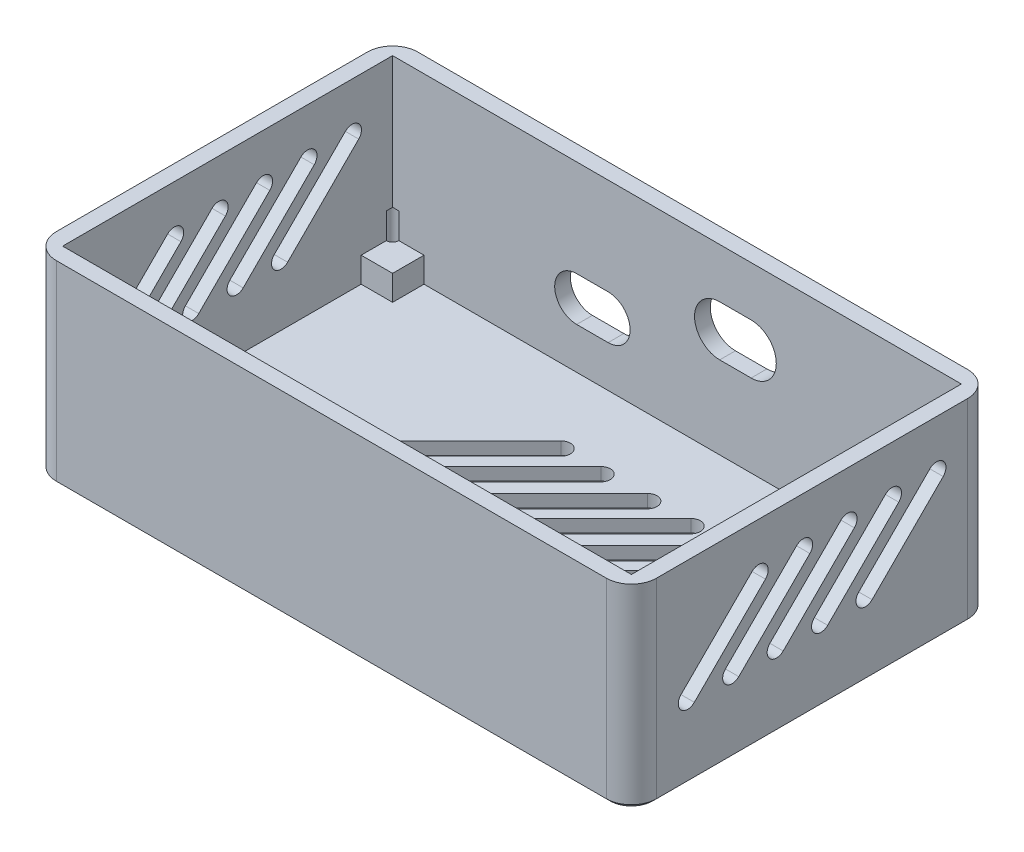
SolidWorks part; units mm, degrees
ref_plane "Front Plane" through (0, 0, 0) normal (0, 0, 1) x (1, 0, 0)
ref_plane "Top Plane" through (0, 0, 0) normal (0, 1, 0) x (1, 0, 0)
ref_plane "Right Plane" through (0, 0, 0) normal (1, 0, 0) x (0, 0, -1)
sketch "Croquis_contorno" plane through (0, 0, 0) normal (0, 1, 0) x (1, 0, 0)
  line L0 (-43.75, -28.75) -> (43.75, -28.75)
  line L1 (47.75, -24.75) -> (47.75, 24.75)
  line L2 (43.75, 28.75) -> (-43.75, 28.75)
  line L3 (-47.75, 24.75) -> (-47.75, -24.75)
  arc A0 (43.75, -28.75) -> (47.75, -24.75) centre (43.75, -24.75) ccw
  arc A1 (47.75, 24.75) -> (43.75, 28.75) centre (43.75, 24.75) ccw
  arc A2 (-43.75, 28.75) -> (-47.75, 24.75) centre (-43.75, 24.75) ccw
  arc A3 (-47.75, -24.75) -> (-43.75, -28.75) centre (-43.75, -24.75) ccw
  dimension "D3" = 4
  dimension "D1" = 95.5
  dimension "D2" = 57.5
extrude "Cuerpo" add sketch "Croquis_contorno" along normal blind 31
ref_plane "Plano_Top Plane_+31" through (0, 31, 0) normal (0, 1, 0) x (1, 0, 0)
sketch "Croquis_hueco_PCB" plane through (0, 31, 0) normal (0, 1, 0) x (1, 0, 0)
  line L1 (-45.25, -26.25) -> (45.25, -26.25)
  line L2 (-45.25, -26.25) -> (-45.25, 26.25)
  line L3 (-45.25, 26.25) -> (45.25, 26.25)
  line L4 (45.25, -26.25) -> (45.25, 26.25)
  line L5 (-45.25, -26.25) -> (45.25, 26.25) construction
  line L6 (-45.25, 26.25) -> (45.25, -26.25) construction
  dimension "D1" = 90.5
  dimension "D2" = 52.5
extrude "Hueco_PCB" cut sketch "Croquis_hueco_PCB" against normal blind 29
ref_plane "Plano_Top Plane_+2" through (0, 2, 0) normal (0, 1, 0) x (1, 0, 0)
sketch "Croquis_apoyos" plane through (0, 2, 0) normal (0, 1, 0) x (1, 0, 0)
  line L0 (45.25, 26.25) -> (-45.25, 26.25) construction
  line L1 (-45.25, -26.25) -> (-40.25, -26.25)
  line L2 (-45.25, -26.25) -> (-45.25, -21.25)
  line L3 (-45.25, -21.25) -> (-40.25, -21.25)
  line L4 (-40.25, -26.25) -> (-40.25, -21.25)
  line L5 (-45.25, -26.25) -> (-40.25, -21.25) construction
  line L6 (-45.25, -21.25) -> (-40.25, -26.25) construction
  line L7 (-45.25, 21.25) -> (-40.25, 21.25)
  line L8 (-45.25, 21.25) -> (-45.25, 26.25)
  line L9 (-45.25, 26.25) -> (-40.25, 26.25)
  line L10 (-40.25, 21.25) -> (-40.25, 26.25)
  line L11 (-45.25, 21.25) -> (-40.25, 26.25) construction
  line L12 (-45.25, 26.25) -> (-40.25, 21.25) construction
  line L13 (45.25, -26.25) -> (45.25, 26.25) construction
  line L14 (40.25, -26.25) -> (45.25, -26.25)
  line L15 (40.25, -26.25) -> (40.25, -21.25)
  line L16 (40.25, -21.25) -> (45.25, -21.25)
  line L17 (45.25, -26.25) -> (45.25, -21.25)
  line L18 (40.25, -26.25) -> (45.25, -21.25) construction
  line L19 (40.25, -21.25) -> (45.25, -26.25) construction
  line L21 (40.25, 21.25) -> (45.25, 21.25)
  line L22 (40.25, 21.25) -> (40.25, 26.25)
  line L23 (40.25, 26.25) -> (45.25, 26.25)
  line L24 (45.25, 21.25) -> (45.25, 26.25)
  line L25 (40.25, 21.25) -> (45.25, 26.25) construction
  line L26 (40.25, 26.25) -> (45.25, 21.25) construction
  point P0 (-42.75, 23.75)
  point P11 (42.75, -23.75)
  point P18 (42.75, 23.75)
  dimension "D1" = 5
  dimension "D2" = 5
extrude "Apoyos_PCB" add sketch "Croquis_apoyos" along normal blind 4
sketch "Croquis_alivios" plane through (0, 2, 0) normal (0, 1, 0) x (1, 0, 0)
  circle A0 centre (-45.25, -26.25) radius 1
  circle A1 centre (-45.25, 26.25) radius 1
  circle A2 centre (45.25, -26.25) radius 1
  circle A3 centre (45.25, 26.25) radius 1
  dimension "D1" = 2
extrude "Alivios_esquinas" cut sketch "Croquis_alivios" along normal blind 8.1
sketch "Croquis_salidas" plane through (0, 0, 0) normal (0, 0, 1) x (1, 0, 0)
  line L0 (6.8, 19.1) -> (11.8, 19.1) construction
  line L1 (6.8, 23.1) -> (11.8, 23.1)
  line L2 (6.8, 15.1) -> (11.8, 15.1)
  line L3 (-15.96, 12.1) -> (-10.96, 12.1) construction
  line L4 (-15.96, 15.6) -> (-10.96, 15.6)
  line L5 (-15.96, 8.6) -> (-10.96, 8.6)
  arc A0 (6.8, 23.1) -> (6.8, 15.1) centre (6.8, 19.1) ccw
  arc A1 (11.8, 15.1) -> (11.8, 23.1) centre (11.8, 19.1) ccw
  arc A2 (-15.96, 15.6) -> (-15.96, 8.6) centre (-15.96, 12.1) ccw
  arc A3 (-10.96, 8.6) -> (-10.96, 15.6) centre (-10.96, 12.1) ccw
  point P2 (9.3, 19.1)
  point P7 (-13.46, 12.1)
  point P14 (0, 0)
extrude "Salidas_USB_y_panel" cut sketch "Croquis_salidas" against normal through all
sketch "Croquis_ventilas" plane through (0, 0, 0) normal (1, 0, 0) x (0, 0, -1)
  line L0 (-19.799, 11.9431) -> (-8.4853, 23.2569) construction
  line L1 (-20.8597, 13.0038) -> (-9.5459, 24.3175)
  line L2 (-18.7383, 10.8825) -> (-7.4246, 22.1962)
  line L3 (-12.7279, 11.9431) -> (-1.4142, 23.2569) construction
  line L4 (-13.7886, 13.0038) -> (-2.4749, 24.3175)
  line L5 (-11.6673, 10.8825) -> (-0.3536, 22.1962)
  line L6 (-5.6569, 11.9431) -> (5.6569, 23.2569) construction
  line L7 (-6.7175, 13.0038) -> (4.5962, 24.3175)
  line L8 (-4.5962, 10.8825) -> (6.7175, 22.1962)
  line L9 (1.4142, 11.9431) -> (12.7279, 23.2569) construction
  line L10 (0.3536, 13.0038) -> (11.6673, 24.3175)
  line L11 (2.4749, 10.8825) -> (13.7886, 22.1962)
  line L12 (8.4853, 11.9431) -> (19.799, 23.2569) construction
  line L13 (7.4246, 13.0038) -> (18.7383, 24.3175)
  line L14 (9.5459, 10.8825) -> (20.8597, 22.1962)
  arc A0 (-20.8597, 13.0038) -> (-18.7383, 10.8825) centre (-19.799, 11.9431) ccw
  arc A1 (-7.4246, 22.1962) -> (-9.5459, 24.3175) centre (-8.4853, 23.2569) ccw
  arc A2 (-13.7886, 13.0038) -> (-11.6673, 10.8825) centre (-12.7279, 11.9431) ccw
  arc A3 (-0.3536, 22.1962) -> (-2.4749, 24.3175) centre (-1.4142, 23.2569) ccw
  arc A4 (-6.7175, 13.0038) -> (-4.5962, 10.8825) centre (-5.6569, 11.9431) ccw
  arc A5 (6.7175, 22.1962) -> (4.5962, 24.3175) centre (5.6569, 23.2569) ccw
  arc A6 (0.3536, 13.0038) -> (2.4749, 10.8825) centre (1.4142, 11.9431) ccw
  arc A7 (13.7886, 22.1962) -> (11.6673, 24.3175) centre (12.7279, 23.2569) ccw
  arc A8 (7.4246, 13.0038) -> (9.5459, 10.8825) centre (8.4853, 11.9431) ccw
  arc A9 (20.8597, 22.1962) -> (18.7383, 24.3175) centre (19.799, 23.2569) ccw
  point P2 (-14.1421, 17.6)
  point P7 (-7.0711, 17.6)
  point P14 (0, 17.6)
  point P21 (7.0711, 17.6)
  point P28 (14.1421, 17.6)
  point P35 (0, 0)
extrude "Ventilas_laterales" cut sketch "Croquis_ventilas" along normal through all and the other way through all
sketch "Croquis_rejilla_piso" plane through (0, 0, 0) normal (0, 1, 0) x (1, 0, 0)
  line L0 (-35.7089, -14.4957) -> (-6.7175, 14.4957) construction
  line L1 (-36.7696, -13.435) -> (-7.7782, 15.5563)
  line L2 (-34.6482, -15.5563) -> (-5.6569, 13.435)
  line L3 (-28.6378, -14.4957) -> (0, 14.1421) construction
  line L4 (-29.6985, -13.435) -> (-1.0607, 15.2028)
  line L5 (-27.5772, -15.5563) -> (1.0607, 13.0815)
  line L6 (-21.2132, -14.4957) -> (7.4246, 14.1421) construction
  line L7 (-22.2739, -13.435) -> (6.364, 15.2028)
  line L8 (-20.1525, -15.5563) -> (8.4853, 13.0815)
  line L9 (-14.3189, -14.4957) -> (14.3189, 14.1421) construction
  line L10 (-15.3796, -13.435) -> (13.2583, 15.2028)
  line L11 (-13.2583, -15.5563) -> (15.3796, 13.0815)
  line L12 (-6.8943, -14.4957) -> (21.7435, 14.1421) construction
  line L13 (-7.955, -13.435) -> (20.6829, 15.2028)
  line L14 (-5.8336, -15.5563) -> (22.8042, 13.0815)
  line L15 (0, -14.4957) -> (28.6378, 14.1421) construction
  line L16 (-1.0607, -13.435) -> (27.5772, 15.2028)
  line L17 (1.0607, -15.5563) -> (29.6985, 13.0815)
  line L18 (6.364, -14.4957) -> (35.5321, 14.6725) construction
  line L19 (5.3033, -13.435) -> (34.4715, 15.7331)
  line L20 (7.4246, -15.5563) -> (36.5928, 13.6118)
  arc A0 (-36.7696, -13.435) -> (-34.6482, -15.5563) centre (-35.7089, -14.4957) ccw
  arc A1 (-5.6569, 13.435) -> (-7.7782, 15.5563) centre (-6.7175, 14.4957) ccw
  arc A2 (-29.6985, -13.435) -> (-27.5772, -15.5563) centre (-28.6378, -14.4957) ccw
  arc A3 (1.0607, 13.0815) -> (-1.0607, 15.2028) centre (0, 14.1421) ccw
  arc A4 (-22.2739, -13.435) -> (-20.1525, -15.5563) centre (-21.2132, -14.4957) ccw
  arc A5 (8.4853, 13.0815) -> (6.364, 15.2028) centre (7.4246, 14.1421) ccw
  arc A6 (-15.3796, -13.435) -> (-13.2583, -15.5563) centre (-14.3189, -14.4957) ccw
  arc A7 (15.3796, 13.0815) -> (13.2583, 15.2028) centre (14.3189, 14.1421) ccw
  arc A8 (-7.955, -13.435) -> (-5.8336, -15.5563) centre (-6.8943, -14.4957) ccw
  arc A9 (22.8042, 13.0815) -> (20.6829, 15.2028) centre (21.7435, 14.1421) ccw
  arc A10 (-1.0607, -13.435) -> (1.0607, -15.5563) centre (0, -14.4957) ccw
  arc A11 (29.6985, 13.0815) -> (27.5772, 15.2028) centre (28.6378, 14.1421) ccw
  arc A12 (5.3033, -13.435) -> (7.4246, -15.5563) centre (6.364, -14.4957) ccw
  arc A13 (36.5928, 13.6118) -> (34.4715, 15.7331) centre (35.5321, 14.6725) ccw
  point P2 (-21.2132, 0)
  point P7 (-14.3189, -0.1768)
  point P14 (-6.8943, -0.1768)
  point P21 (0, -0.1768)
  point P28 (7.4246, -0.1768)
  point P35 (14.3189, -0.1768)
  point P42 (20.948, 0.0884)
  point P49 (0, 0)
extrude "Rejilla_piso" cut sketch "Croquis_rejilla_piso" along normal blind 2
chamfer "Chaflan_base" distance 0.6 angle 45 8 edges at (0, 0, 28.75) (46.5784, 0, 27.5784) (47.75, 0, 0) (46.5784, 0, -27.5784) (0, 0, -28.75) (-46.5784, 0, -27.5784) (-47.75, 0, 0) (-46.5784, 0, 27.5784) tangent propagation no
